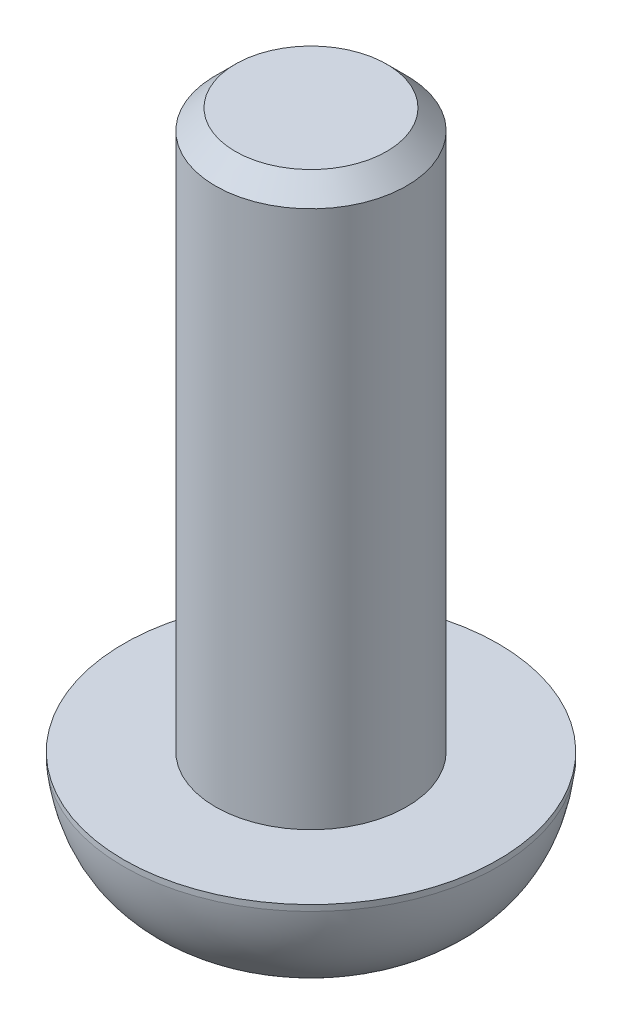
SolidWorks part; units mm, degrees
ref_plane "Front Plane" through (0, 0, 0) normal (0, 0, 1) x (1, 0, 0)
ref_plane "Top Plane" through (0, 0, 0) normal (0, 1, 0) x (1, 0, 0)
ref_plane "Right Plane" through (0, 0, 0) normal (1, 0, 0) x (0, 0, -1)
sketch "Sketch1" plane through (0, 0, 0) normal (0, 1, 0) x (1, 0, 0)
  circle A0 centre (0, 0) radius 4.7
  dimension "D1" = 9.4
extrude "Boss-Extrude1" add sketch "Sketch1" along normal blind 3
sketch "Sketch2" plane through (0, 3, 0) normal (0, 1, 0) x (1, 0, 0)
  circle A0 centre (0, 0) radius 2.4
  dimension "D1" = 4.8
extrude "Boss-Extrude2" add sketch "Sketch2" along normal blind 14
sketch "Sketch3" plane through (0, 0, 0) normal (0, 0, 1) x (1, 0, 0)
  line L0 (0, 0) -> (0, 3) construction
  line L1 (4.7, 3) -> (-4.7, 3) construction
  line L3 (-4.7, 0) -> (4.7, 0) construction
  line L4 (4.7, 0) -> (4.7, 3) construction
  line L5 (2.35, 0) -> (4.7, 0)
  line L6 (4.7, 0) -> (4.7, 2.85)
  spline S0 degree 2 poles (2.35, 0) (4.4325, 0.5996) (4.7, 2.85) knots 0 0 0 1 1 1
  dimension "D1" = 4.7
  dimension "D2" = 0.15
revolve "Cut-Revolve1" cut sketch "Sketch3" angle 360 about L0
sketch "Sketch4" plane through (0, 0, 0) normal (0, -1, 0) x (1, 0, 0)
  line L1 (0, 1.7321) -> (-1.5, 0.866)
  line L2 (-1.5, 0.866) -> (-1.5, -0.866)
  line L3 (-1.5, -0.866) -> (0, -1.7321)
  line L4 (0, -1.7321) -> (1.5, -0.866)
  line L5 (1.5, -0.866) -> (1.5, 0.866)
  line L6 (1.5, 0.866) -> (0, 1.7321)
  circle A0 centre (0, 0) radius 1.5 construction
  dimension "D1" = 3
extrude "Cut-Extrude1" cut sketch "Sketch4" against normal blind 1.5
chamfer "Chamfer1" distance 0.5 angle 45 1 edges at (0, 17, 2.4)
